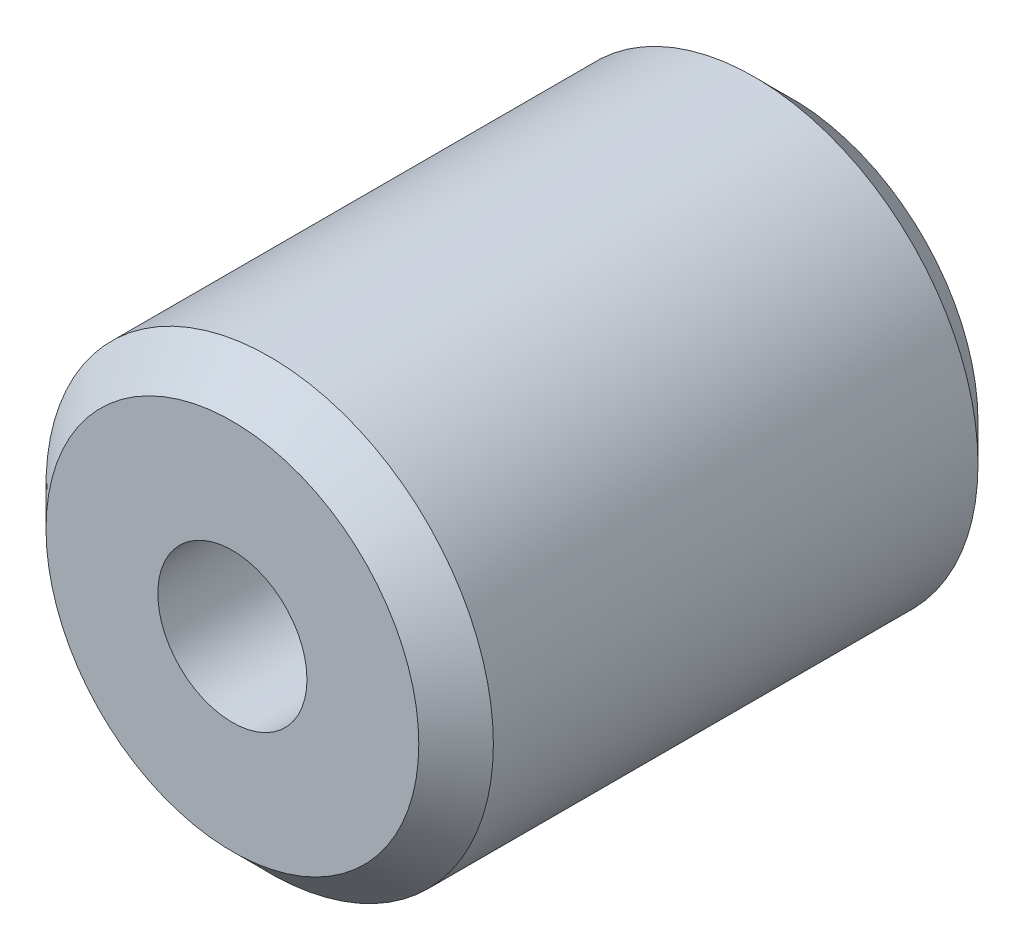
SolidWorks part; units mm, degrees
material "ABS"
ref_plane "Front Plane" through (0, 0, 0) normal (0, 0, 1) x (1, 0, 0)
ref_plane "Top Plane" through (0, 0, 0) normal (0, 1, 0) x (1, 0, 0)
ref_plane "Right Plane" through (0, 0, 0) normal (1, 0, 0) x (0, 0, -1)
sketch "Sketch1" plane through (0, 0, 0) normal (0, 0, 1) x (1, 0, 0)
  circle A0 centre (0, 0) radius 6
  dimension "D1" = 12
extrude "Boss-Extrude1" add sketch "Sketch1" along normal blind 15
sketch "Sketch2" plane through (0, 0, 0) normal (0, 0, 1) x (1, 0, 0)
  circle A0 centre (0, 0) radius 2
  dimension "D1" = 4
extrude "Cut-Extrude1" cut sketch "Sketch2" along normal through all
chamfer "Chamfer1" distance 1 angle 45 2 edges at (6, 0, 0) (6, 0, 15)
